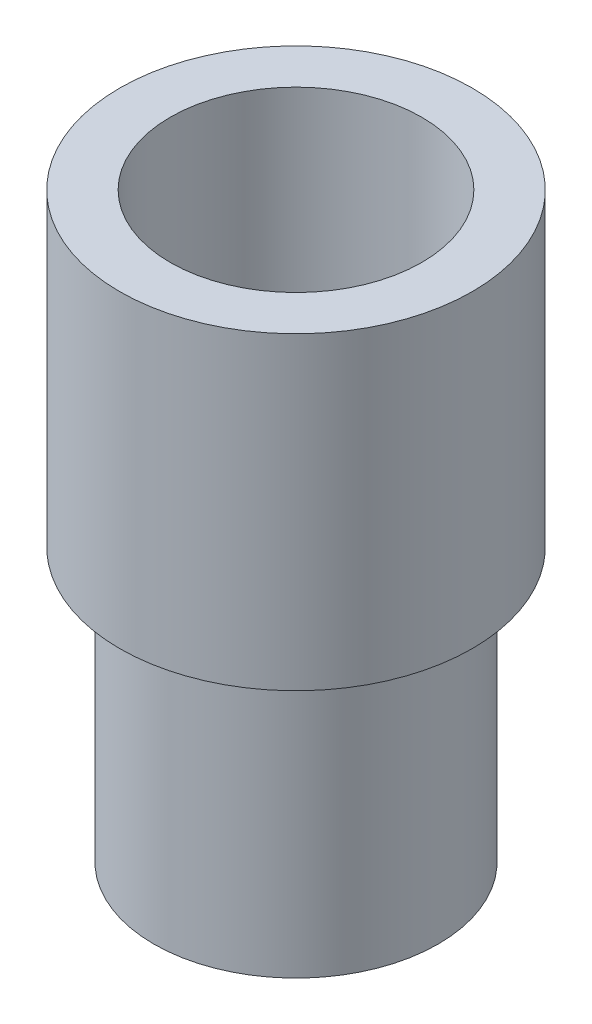
SolidWorks part; units mm, degrees
material "AISI 304"
ref_plane "Front Plane" through (0, 0, 0) normal (0, 0, 1) x (1, 0, 0)
ref_plane "Top Plane" through (0, 0, 0) normal (0, 1, 0) x (1, 0, 0)
ref_plane "Right Plane" through (0, 0, 0) normal (1, 0, 0) x (0, 0, -1)
sketch "Sketch1" plane through (0, 0, 0) normal (0, 0, 1) x (1, 0, 0)
  line L0 (0, 0) -> (0, 65) construction
  line L2 (14.0462, 0) -> (15.875, 0)
  line L3 (14.0462, 0) -> (14.0462, 30.48)
  line L4 (14.0462, 30.48) -> (15.875, 30.48)
  line L5 (15.875, 0) -> (15.875, 30.48)
  line L6 (14.0462, 30.48) -> (19.685, 30.48)
  line L7 (14.0462, 30.48) -> (14.0462, 65)
  line L8 (14.0462, 65) -> (19.685, 65)
  line L9 (19.685, 30.48) -> (19.685, 65)
  line L10 (14.0462, 40.48) -> (0, 40.48)
  line L11 (14.0462, 40.48) -> (14.0462, 30.48)
  line L12 (14.0462, 30.48) -> (0, 30.48)
  line L13 (0, 40.48) -> (0, 30.48)
  dimension "D1" = 65
  dimension "D2" = 31.75
  dimension "D3" = 1.8288
  dimension "D4" = 30.48
  dimension "D5" = 3.81
  dimension "D6" = 10
revolve "Revolve1" add sketch "Sketch1" angle 360 about L0 region at (14.9606, 15.24, 0) region at (16.8656, 47.74, 0) region at (7.0231, 35.48, 0)
